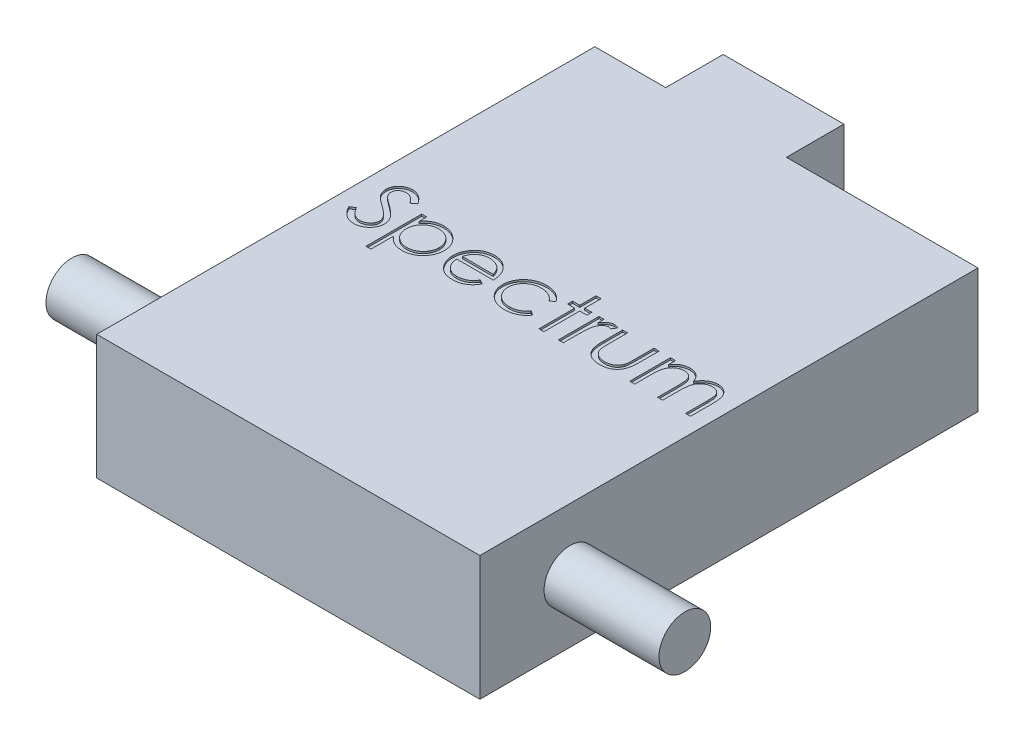
SolidWorks part; units mm, degrees
ref_plane "Front Plane" through (0, 0, 0) normal (0, 0, 1) x (1, 0, 0)
ref_plane "Top Plane" through (0, 0, 0) normal (0, 1, 0) x (1, 0, 0)
ref_plane "Right Plane" through (0, 0, 0) normal (1, 0, 0) x (0, 0, -1)
sketch "Sketch1" plane through (0, 0, 0) normal (0, 1, 0) x (1, 0, 0)
  line L1 (-10, 13) -> (10, 13)
  line L2 (-10, 13) -> (-10, -13)
  line L3 (-10, -13) -> (10, -13)
  line L4 (10, 13) -> (10, -13)
  line L5 (-10, 13) -> (10, -13) construction
  line L6 (-10, -13) -> (10, 13) construction
  point P0 (0, 0)
  dimension "D1" = 20
  dimension "D2" = 26
extrude "Boss-Extrude1" add sketch "Sketch1" along normal blind 6.5
sketch "Sketch2" plane through (10, 0, 0) normal (1, 0, 0) x (0, 0, -1)
  line L0 (-8.3, 6.5) -> (-8.3, 0) construction
  line L1 (-13, 6.5) -> (13, 6.5) construction
  line L2 (-13, 0) -> (13, 0) construction
  line L3 (-13, 6.5) -> (-13, 0) construction
  circle A0 centre (-8.3, 3.25) radius 1.35
  dimension "D2" = 2.7
  dimension "D1" = 4.7
extrude "Boss-Extrude2" add sketch "Sketch2" along normal blind 6
ref_axis "Axis1" through (0, 6.5, 13) along (0, -1, 0)
ref_plane "Plane1" through (0, 0, 0) normal (1, 0, 0) x (0, 0, -1)
mirror "Mirror1" about plane through (0, 0, 0) normal (1, 0, 0) of "Boss-Extrude2"
sketch "Sketch3" plane through (0, 0, -13) normal (0, 0, -1) x (-1, 0, 0)
  line L0 (-10, 6.5) -> (10, 6.5) construction
  line L1 (0, 3.3) -> (6.3, 3.3)
  line L2 (0, 3.3) -> (0, 6.5)
  line L3 (0, 6.5) -> (6.3, 6.5)
  line L4 (6.3, 3.3) -> (6.3, 6.5)
  line L5 (0, 3.3) -> (6.3, 6.5) construction
  line L6 (0, 6.5) -> (6.3, 3.3) construction
  line L7 (10, 6.5) -> (10, 0) construction
  line L8 (10, 1.9) -> (10, 4.6) construction
  point P0 (3.15, 4.9)
  dimension "D1" = 3.7
  dimension "D2" = 10
  dimension "D3" = 3.2
extrude "Boss-Extrude3" add sketch "Sketch3" along normal blind 3
sketch "Sketch4" plane through (0, 6.5, 0) normal (0, 1, 0) x (1, 0, 0)
  text T0 "Spectrum" font "Century Gothic" height in points 11
extrude "Cut-Extrude1" cut sketch "Sketch4" against normal blind 0.1
